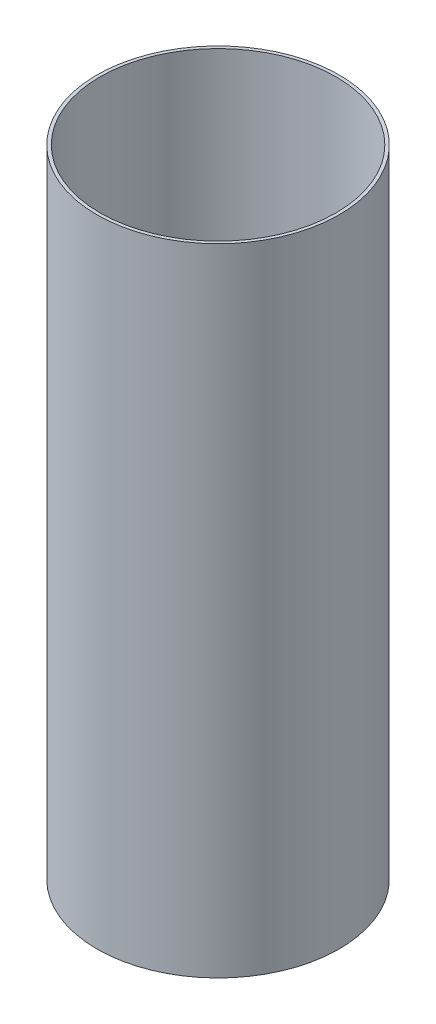
SolidWorks part; units mm, degrees
material "A-Glass Fiber"
ref_plane "Front Plane" through (0, 0, 0) normal (0, 0, 1) x (1, 0, 0)
ref_plane "Top Plane" through (0, 0, 0) normal (0, 1, 0) x (1, 0, 0)
ref_plane "Right Plane" through (0, 0, 0) normal (1, 0, 0) x (0, 0, -1)
sketch "Sketch1" plane through (0, 0, 0) normal (0, 1, 0) x (1, 0, 0)
  circle A0 centre (0, 0) radius 74.2
  circle A1 centre (0, 0) radius 76.2
  dimension "D1" = 148.4
  dimension "D2" = 152.4
extrude "Boss-Extrude1" add sketch "Sketch1" along normal blind 400
